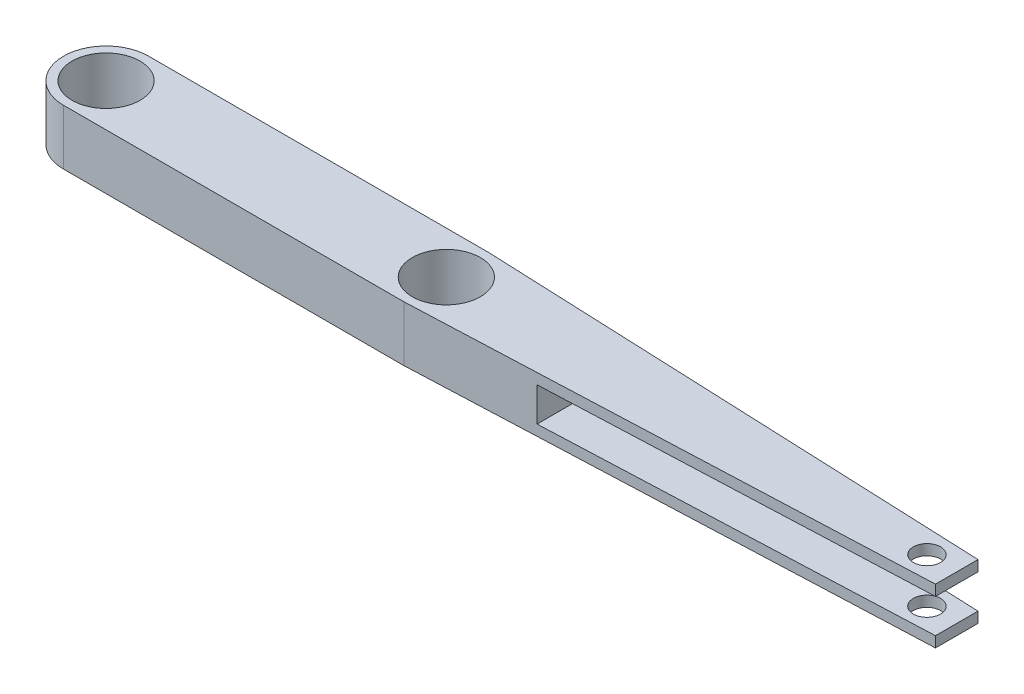
SolidWorks part; units mm, degrees
ref_plane "前视基准面" through (0, 0, 0) normal (0, 0, 1) x (1, 0, 0)
ref_plane "上视基准面" through (0, 0, 0) normal (0, 1, 0) x (1, 0, 0)
ref_plane "右视基准面" through (0, 0, 0) normal (1, 0, 0) x (0, 0, -1)
other "Configuration Table"
sketch "草图1" plane through (0, 0, 0) normal (0, 1, 0) x (1, 0, 0)
  line L0 (0, 0) -> (40, 0)
  line L1 (40, 0) -> (100, 0)
  line L2 (0, 5) -> (40, 5)
  line L3 (40, 5) -> (0, 5)
  line L4 (40, 5) -> (100, 2.5)
  line L5 (100, 0) -> (100, 2.5)
  line L6 (40, -5) -> (100, -2.5)
  line L7 (0, -5) -> (40, -5)
  line L8 (100, 0) -> (100, -2.5)
  circle A0 centre (0, 0) radius 4
  circle A1 centre (0, 0) radius 5
  circle A2 centre (40, 0) radius 4
  circle A3 centre (40, 0) radius 5
  dimension "D1" = 8
  dimension "D2" = 10
  dimension "D4" = 8
  dimension "D5" = 10
  dimension "D3" = 40
  dimension "D6" = 2.5
extrude "凸台-拉伸1" add sketch "草图1" along normal blind 6.5 contours A3 L1 L4 | A3 L6 L1 | A3 L1 A2 L0 | L1 A3 L0 A2 | A3 L2 A1 L0 | A3 L0 A1 L7 | A1 A0 region at (3.4355, 0, 3.4355) region at (20, 0, -2.5923) region at (20, 0, 2.5923) region at (36.5435, 0, -3.4565) region at (35.5, 0, 0.1118) region at (69.0132, 0, -1.9275) region at (69.0132, 0, 1.9275)
sketch "草图2" plane through (0, 6.5, 0) normal (0, 1, 0) x (1, 0, 0)
  line L0 (100, 0) -> (80, 0)
  line L1 (100, -2.5) -> (100, 2.5) construction
  line L2 (100, 0) -> (96.5, 0)
  line L3 (60, -1.5) -> (100, -1.5)
  line L4 (60, -1.5) -> (60, 1.5)
  line L5 (60, 1.5) -> (100, 1.5)
  line L6 (100, -1.5) -> (100, 1.5)
  line L7 (80, 1.5) -> (80, -1.5) construction
  line L8 (60, 0) -> (100, 0) construction
  circle A0 centre (96.5, 0) radius 1.6
  dimension "D4" = 3.2
  dimension "D1" = 20
  dimension "D2" = 3
  dimension "D3" = 3.5
extrude "切除-拉伸3" cut sketch "草图2" against normal blind 10 contours L2 A0 L5 L0 | L3 A0 L2 L0 | A0 region at (96.5, 6.5, 0.6628) region at (96.5, 6.5, -0.6628)
sketch "草图3" plane through (0.2773, 0, -6.6551) normal (0.0416, 0, -0.9991) x (-0.9991, 0, -0.0416)
  line L0 (-99.8092, 3.25) -> (-54.8092, 3.25)
  line L1 (-99.8092, 6.5) -> (-99.8092, 0) construction
  line L2 (-54.8092, 3.25) -> (-54.8092, 1.25)
  line L3 (-54.8092, 3.25) -> (-54.8092, 5.25)
  line L4 (-54.8092, 5.25) -> (-99.8092, 5.25)
  line L5 (-99.8092, 5.25) -> (-99.8092, 3.25)
  line L6 (-99.8092, 3.25) -> (-99.8092, 1.25)
  line L7 (-99.8092, 1.25) -> (-54.8092, 1.25)
  dimension "D1" = 45
  dimension "D2" = 2
  dimension "D3" = 2
  dimension "D4" = 2
ref_plane "基准面1" through (100, 6.5, 2.5) normal (0.9991, 0, -0.0416) x (-0.0416, 0, -0.9991)
sketch "草图6" plane through (0, 0, -5) normal (0, 0, -1) x (-1, 0, 0)
  line L1 (-55.039, 5.25) -> (-100, 5.25)
  line L2 (-55.039, 5.25) -> (-55.039, 1.25)
  line L3 (-55.039, 1.25) -> (-100, 1.25)
  line L4 (-100, 5.25) -> (-100, 1.25)
  line L5 (-55.039, 5.25) -> (-100, 1.25) construction
  line L6 (-55.039, 1.25) -> (-100, 5.25) construction
  point P4 (-77.5195, 3.25)
extrude "切除-拉伸4" cut sketch "草图6" against normal blind 10
